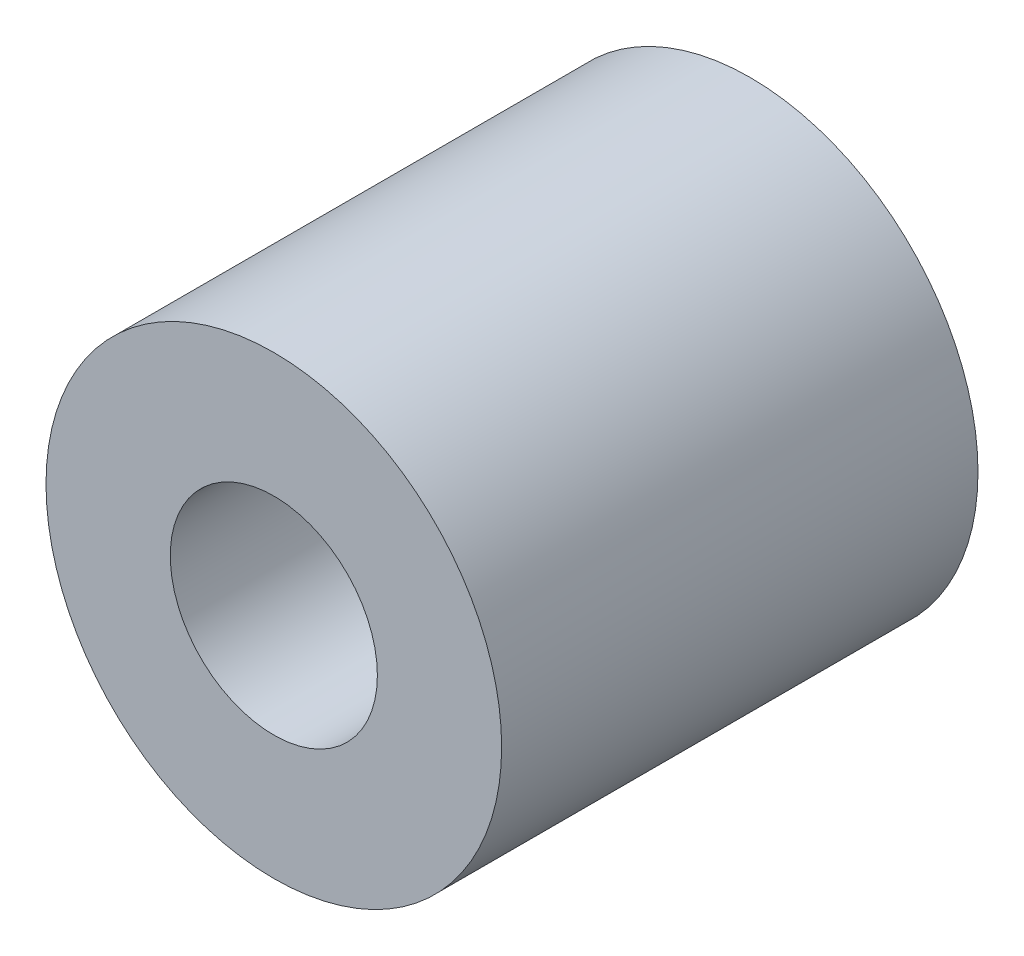
SolidWorks part; units mm, degrees
ref_plane "Front Plane" through (0, 0, 0) normal (0, 0, 1) x (1, 0, 0)
ref_plane "Top Plane" through (0, 0, 0) normal (0, 1, 0) x (1, 0, 0)
ref_plane "Right Plane" through (0, 0, 0) normal (1, 0, 0) x (0, 0, -1)
sketch "Sketch1" plane through (0, 0, 0) normal (0, 0, 1) x (1, 0, 0)
  circle A0 centre (0, 0) radius 2.5
  circle A1 centre (0, 0) radius 5.5
  dimension "D1" = 11
  dimension "D2" = 5
extrude "Boss-Extrude1" add sketch "Sketch1" along normal blind 11.5
